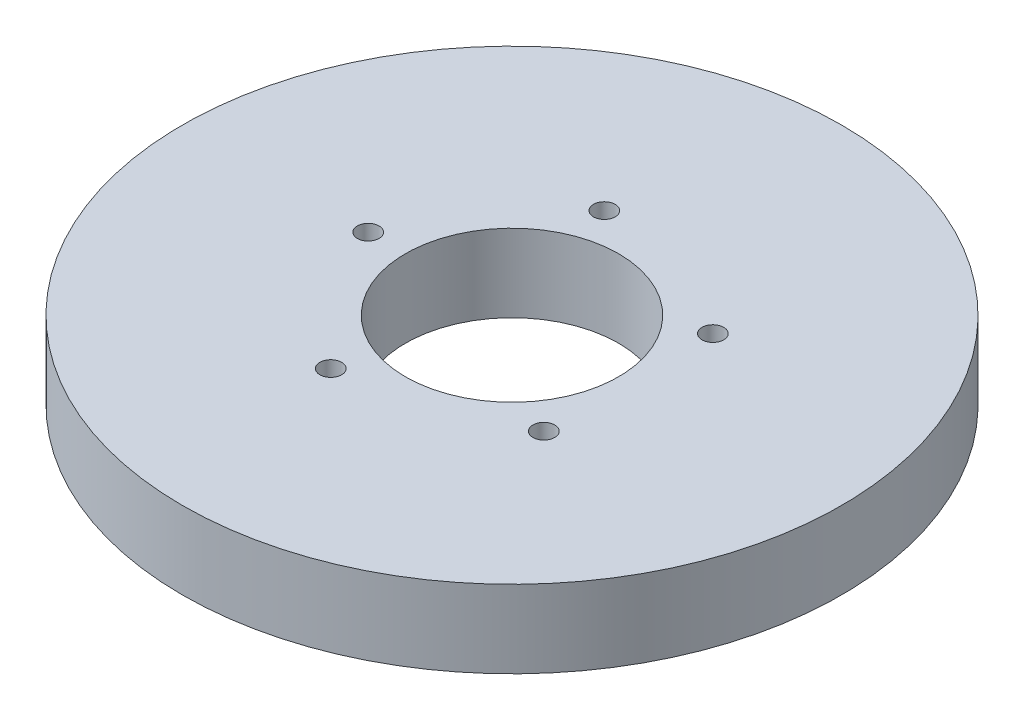
SolidWorks part; units mm, degrees
ref_plane "Front Plane" through (0, 0, 0) normal (0, 0, 1) x (1, 0, 0)
ref_plane "Top Plane" through (0, 0, 0) normal (0, 1, 0) x (1, 0, 0)
ref_plane "Right Plane" through (0, 0, 0) normal (1, 0, 0) x (0, 0, -1)
sketch "Sketch1" plane through (0, 0, 0) normal (0, 1, 0) x (1, 0, 0)
  circle A0 centre (0, 0) radius 85
  dimension "FLANGE_OD" = 170
extrude "Boss-Extrude1" add sketch "Sketch1" along normal blind 20
sketch "Sketch2" plane through (0, 0, 0) normal (0, 1, 0) x (1, 0, 0)
  circle A0 centre (0, 0) radius 27.5
  dimension "BORE_D" = 55
extrude "Cut-Extrude1" cut sketch "Sketch2" along normal through all
sketch "Sketch3" plane through (0, 20, 0) normal (0, 1, 0) x (1, 0, 0)
  circle A0 centre (0, 0) radius 37.0935 construction
  circle A1 centre (-37.0935, 0) radius 2.8048
  dimension "BOLT_D" = 5.6095
  dimension "BOLT_PCD" = 74.1869
extrude "Cut-Extrude2" cut sketch "Sketch3" against normal blind 17.6649
pattern_circular "CirPattern1" count 5 over 360 about axis through (0, 0, 0) along (0, 1, 0) of "Cut-Extrude2"
